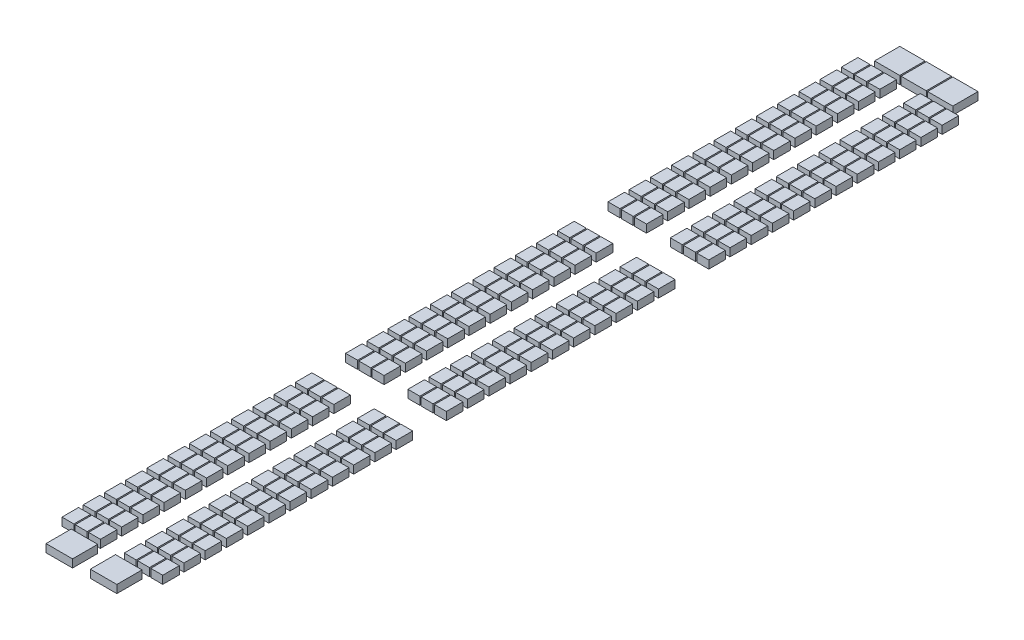
SolidWorks part; units mm, degrees
ref_plane "Front Plane" through (0, 0, 0) normal (0, 0, 1) x (1, 0, 0)
ref_plane "Top Plane" through (0, 0, 0) normal (0, 1, 0) x (1, 0, 0)
ref_plane "Right Plane" through (0, 0, 0) normal (1, 0, 0) x (0, 0, -1)
sketch "Sketch1" plane through (0, 0, 0) normal (0, 1, 0) x (1, 0, 0)
  line L0 (1993.392, 0) -> (-1993.392, 0) construction
  line L1 (1993.392, -15290.8) -> (-1993.392, -15290.8) construction
  line L2 (1993.392, -15290.8) -> (1993.392, 15290.8) construction
  line L3 (1993.392, 15290.8) -> (-1993.392, 15290.8) construction
  line L4 (-1993.392, -15290.8) -> (-1993.392, 15290.8) construction
  line L5 (-1993.392, 5630.3333) -> (1993.392, 5630.3333) construction
  line L6 (-1993.392, 4563.5333) -> (1993.392, 4563.5333) construction
  line L11 (0, -15290.8) -> (0, 15290.8) construction
  line L12 (-1993.392, -4563.5333) -> (1993.392, -4563.5333) construction
  line L13 (-1993.392, -5630.3333) -> (1993.392, -5630.3333) construction
  line L14 (-1421.892, -14613.4667) -> (-964.692, -14613.4667)
  line L15 (-1929.892, -14613.4667) -> (-1472.692, -14613.4667)
  line L16 (-1929.892, -14613.4667) -> (-1929.892, -15248.4667)
  line L17 (-1929.892, -15248.4667) -> (-1472.692, -15248.4667)
  line L18 (-1472.692, -14613.4667) -> (-1472.692, -15248.4667)
  line L19 (-1421.892, -14613.4667) -> (-1421.892, -15248.4667)
  line L20 (-1421.892, -15248.4667) -> (-964.692, -15248.4667)
  line L21 (-964.692, -14613.4667) -> (-964.692, -15248.4667)
  line L22 (-913.892, -14613.4667) -> (-456.692, -14613.4667)
  line L23 (-913.892, -14613.4667) -> (-913.892, -15248.4667)
  line L24 (-913.892, -15248.4667) -> (-456.692, -15248.4667)
  line L25 (-456.692, -14613.4667) -> (-456.692, -15248.4667)
  line L26 (-1421.892, -13800.6667) -> (-964.692, -13800.6667)
  line L27 (-1421.892, -13800.6667) -> (-1421.892, -14435.6667)
  line L28 (-1421.892, -14435.6667) -> (-964.692, -14435.6667)
  line L29 (-964.692, -13800.6667) -> (-964.692, -14435.6667)
  line L30 (-913.892, -13800.6667) -> (-456.692, -13800.6667)
  line L31 (-913.892, -13800.6667) -> (-913.892, -14435.6667)
  line L32 (-913.892, -14435.6667) -> (-456.692, -14435.6667)
  line L33 (-456.692, -13800.6667) -> (-456.692, -14435.6667)
  line L34 (-1421.892, -12987.8667) -> (-964.692, -12987.8667)
  line L35 (-1421.892, -12987.8667) -> (-1421.892, -13622.8667)
  line L36 (-1421.892, -13622.8667) -> (-964.692, -13622.8667)
  line L37 (-964.692, -12987.8667) -> (-964.692, -13622.8667)
  line L38 (-913.892, -12987.8667) -> (-456.692, -12987.8667)
  line L39 (-913.892, -12987.8667) -> (-913.892, -13622.8667)
  line L40 (-913.892, -13622.8667) -> (-456.692, -13622.8667)
  line L41 (-456.692, -12987.8667) -> (-456.692, -13622.8667)
  line L42 (-1929.892, -13800.6667) -> (-1472.692, -13800.6667)
  line L43 (-1929.892, -13800.6667) -> (-1929.892, -14435.6667)
  line L44 (-1929.892, -14435.6667) -> (-1472.692, -14435.6667)
  line L45 (-1472.692, -13800.6667) -> (-1472.692, -14435.6667)
  line L46 (-1929.892, -12987.8667) -> (-1472.692, -12987.8667)
  line L47 (-1929.892, -12987.8667) -> (-1929.892, -13622.8667)
  line L48 (-1929.892, -13622.8667) -> (-1472.692, -13622.8667)
  line L49 (-1472.692, -12987.8667) -> (-1472.692, -13622.8667)
  line L50 (-1929.892, -12175.0667) -> (-1472.692, -12175.0667)
  line L51 (-1929.892, -12175.0667) -> (-1929.892, -12810.0667)
  line L52 (-1929.892, -12810.0667) -> (-1472.692, -12810.0667)
  line L53 (-1472.692, -12175.0667) -> (-1472.692, -12810.0667)
  line L54 (-1421.892, -12175.0667) -> (-964.692, -12175.0667)
  line L55 (-1421.892, -12175.0667) -> (-1421.892, -12810.0667)
  line L56 (-1421.892, -12810.0667) -> (-964.692, -12810.0667)
  line L57 (-964.692, -12175.0667) -> (-964.692, -12810.0667)
  line L58 (-913.892, -12175.0667) -> (-456.692, -12175.0667)
  line L59 (-913.892, -12175.0667) -> (-913.892, -12810.0667)
  line L60 (-913.892, -12810.0667) -> (-456.692, -12810.0667)
  line L61 (-456.692, -12175.0667) -> (-456.692, -12810.0667)
  line L62 (-1929.892, -11362.2667) -> (-1472.692, -11362.2667)
  line L63 (-1929.892, -11362.2667) -> (-1929.892, -11997.2667)
  line L64 (-1929.892, -11997.2667) -> (-1472.692, -11997.2667)
  line L65 (-1472.692, -11362.2667) -> (-1472.692, -11997.2667)
  line L66 (-1421.892, -11362.2667) -> (-964.692, -11362.2667)
  line L67 (-1421.892, -11362.2667) -> (-1421.892, -11997.2667)
  line L68 (-1421.892, -11997.2667) -> (-964.692, -11997.2667)
  line L69 (-964.692, -11362.2667) -> (-964.692, -11997.2667)
  line L70 (-913.892, -11362.2667) -> (-456.692, -11362.2667)
  line L71 (-913.892, -11362.2667) -> (-913.892, -11997.2667)
  line L72 (-913.892, -11997.2667) -> (-456.692, -11997.2667)
  line L73 (-456.692, -11362.2667) -> (-456.692, -11997.2667)
  line L74 (-1929.892, -10549.4667) -> (-1472.692, -10549.4667)
  line L75 (-1929.892, -10549.4667) -> (-1929.892, -11184.4667)
  line L76 (-1929.892, -11184.4667) -> (-1472.692, -11184.4667)
  line L77 (-1472.692, -10549.4667) -> (-1472.692, -11184.4667)
  line L78 (-1421.892, -10549.4667) -> (-964.692, -10549.4667)
  line L79 (-1421.892, -10549.4667) -> (-1421.892, -11184.4667)
  line L80 (-1421.892, -11184.4667) -> (-964.692, -11184.4667)
  line L81 (-964.692, -10549.4667) -> (-964.692, -11184.4667)
  line L82 (-913.892, -10549.4667) -> (-456.692, -10549.4667)
  line L83 (-913.892, -10549.4667) -> (-913.892, -11184.4667)
  line L84 (-913.892, -11184.4667) -> (-456.692, -11184.4667)
  line L85 (-456.692, -10549.4667) -> (-456.692, -11184.4667)
  line L86 (-1929.892, -9736.6667) -> (-1472.692, -9736.6667)
  line L87 (-1929.892, -9736.6667) -> (-1929.892, -10371.6667)
  line L88 (-1929.892, -10371.6667) -> (-1472.692, -10371.6667)
  line L89 (-1472.692, -9736.6667) -> (-1472.692, -10371.6667)
  line L90 (-1421.892, -9736.6667) -> (-964.692, -9736.6667)
  line L91 (-1421.892, -9736.6667) -> (-1421.892, -10371.6667)
  line L92 (-1421.892, -10371.6667) -> (-964.692, -10371.6667)
  line L93 (-964.692, -9736.6667) -> (-964.692, -10371.6667)
  line L94 (-913.892, -9736.6667) -> (-456.692, -9736.6667)
  line L95 (-913.892, -9736.6667) -> (-913.892, -10371.6667)
  line L96 (-913.892, -10371.6667) -> (-456.692, -10371.6667)
  line L97 (-456.692, -9736.6667) -> (-456.692, -10371.6667)
  line L98 (-1929.892, -8923.8667) -> (-1472.692, -8923.8667)
  line L99 (-1929.892, -8923.8667) -> (-1929.892, -9558.8667)
  line L100 (-1929.892, -9558.8667) -> (-1472.692, -9558.8667)
  line L101 (-1472.692, -8923.8667) -> (-1472.692, -9558.8667)
  line L102 (-1421.892, -8923.8667) -> (-964.692, -8923.8667)
  line L103 (-1421.892, -8923.8667) -> (-1421.892, -9558.8667)
  line L104 (-1421.892, -9558.8667) -> (-964.692, -9558.8667)
  line L105 (-964.692, -8923.8667) -> (-964.692, -9558.8667)
  line L106 (-913.892, -8923.8667) -> (-456.692, -8923.8667)
  line L107 (-913.892, -8923.8667) -> (-913.892, -9558.8667)
  line L108 (-913.892, -9558.8667) -> (-456.692, -9558.8667)
  line L109 (-456.692, -8923.8667) -> (-456.692, -9558.8667)
  line L110 (-1929.892, -8111.0667) -> (-1472.692, -8111.0667)
  line L111 (-1929.892, -8111.0667) -> (-1929.892, -8746.0667)
  line L112 (-1929.892, -8746.0667) -> (-1472.692, -8746.0667)
  line L113 (-1472.692, -8111.0667) -> (-1472.692, -8746.0667)
  line L114 (-1421.892, -8111.0667) -> (-964.692, -8111.0667)
  line L115 (-1421.892, -8111.0667) -> (-1421.892, -8746.0667)
  line L116 (-1421.892, -8746.0667) -> (-964.692, -8746.0667)
  line L117 (-964.692, -8111.0667) -> (-964.692, -8746.0667)
  line L118 (-913.892, -8111.0667) -> (-456.692, -8111.0667)
  line L119 (-913.892, -8111.0667) -> (-913.892, -8746.0667)
  line L120 (-913.892, -8746.0667) -> (-456.692, -8746.0667)
  line L121 (-456.692, -8111.0667) -> (-456.692, -8746.0667)
  line L122 (-1929.892, -7298.2667) -> (-1472.692, -7298.2667)
  line L123 (-1929.892, -7298.2667) -> (-1929.892, -7933.2667)
  line L124 (-1929.892, -7933.2667) -> (-1472.692, -7933.2667)
  line L125 (-1472.692, -7298.2667) -> (-1472.692, -7933.2667)
  line L126 (-1421.892, -7298.2667) -> (-964.692, -7298.2667)
  line L127 (-1421.892, -7298.2667) -> (-1421.892, -7933.2667)
  line L128 (-1421.892, -7933.2667) -> (-964.692, -7933.2667)
  line L129 (-964.692, -7298.2667) -> (-964.692, -7933.2667)
  line L130 (-913.892, -7298.2667) -> (-456.692, -7298.2667)
  line L131 (-913.892, -7298.2667) -> (-913.892, -7933.2667)
  line L132 (-913.892, -7933.2667) -> (-456.692, -7933.2667)
  line L133 (-456.692, -7298.2667) -> (-456.692, -7933.2667)
  line L134 (-1929.892, -6485.4667) -> (-1472.692, -6485.4667)
  line L135 (-1929.892, -6485.4667) -> (-1929.892, -7120.4667)
  line L136 (-1929.892, -7120.4667) -> (-1472.692, -7120.4667)
  line L137 (-1472.692, -6485.4667) -> (-1472.692, -7120.4667)
  line L138 (-1421.892, -6485.4667) -> (-964.692, -6485.4667)
  line L139 (-1421.892, -6485.4667) -> (-1421.892, -7120.4667)
  line L140 (-1421.892, -7120.4667) -> (-964.692, -7120.4667)
  line L141 (-964.692, -6485.4667) -> (-964.692, -7120.4667)
  line L142 (-913.892, -6485.4667) -> (-456.692, -6485.4667)
  line L143 (-913.892, -6485.4667) -> (-913.892, -7120.4667)
  line L144 (-913.892, -7120.4667) -> (-456.692, -7120.4667)
  line L145 (-456.692, -6485.4667) -> (-456.692, -7120.4667)
  line L146 (-1929.892, -5672.6667) -> (-1472.692, -5672.6667)
  line L147 (-1929.892, -5672.6667) -> (-1929.892, -6307.6667)
  line L148 (-1929.892, -6307.6667) -> (-1472.692, -6307.6667)
  line L149 (-1472.692, -5672.6667) -> (-1472.692, -6307.6667)
  line L150 (-1421.892, -5672.6667) -> (-964.692, -5672.6667)
  line L151 (-1421.892, -5672.6667) -> (-1421.892, -6307.6667)
  line L152 (-1421.892, -6307.6667) -> (-964.692, -6307.6667)
  line L153 (-964.692, -5672.6667) -> (-964.692, -6307.6667)
  line L154 (-913.892, -5672.6667) -> (-456.692, -5672.6667)
  line L155 (-913.892, -5672.6667) -> (-913.892, -6307.6667)
  line L156 (-913.892, -6307.6667) -> (-456.692, -6307.6667)
  line L157 (-456.692, -5672.6667) -> (-456.692, -6307.6667)
  line L158 (-456.692, -5672.6667) -> (-456.692, -15248.4667) construction
  line L159 (-456.692, -10460.5667) -> (2544.9668, -10460.5667) construction
  line L160 (-1929.892, -3746.5) -> (-1472.692, -3746.5)
  line L161 (-1929.892, -3746.5) -> (-1929.892, -4381.5)
  line L162 (-1929.892, -4381.5) -> (-1472.692, -4381.5)
  line L163 (-1472.692, -3746.5) -> (-1472.692, -4381.5)
  line L164 (-1421.892, -3746.5) -> (-964.692, -3746.5)
  line L165 (-1421.892, -3746.5) -> (-1421.892, -4381.5)
  line L166 (-1421.892, -4381.5) -> (-964.692, -4381.5)
  line L167 (-964.692, -3746.5) -> (-964.692, -4381.5)
  line L168 (-913.892, -3746.5) -> (-456.692, -3746.5)
  line L169 (-913.892, -3746.5) -> (-913.892, -4381.5)
  line L170 (-913.892, -4381.5) -> (-456.692, -4381.5)
  line L171 (-456.692, -3746.5) -> (-456.692, -4381.5)
  line L172 (-1421.892, -2933.7) -> (-964.692, -2933.7)
  line L173 (-1421.892, -2933.7) -> (-1421.892, -3568.7)
  line L174 (-1421.892, -3568.7) -> (-964.692, -3568.7)
  line L175 (-964.692, -2933.7) -> (-964.692, -3568.7)
  line L176 (-913.892, -2933.7) -> (-456.692, -2933.7)
  line L177 (-913.892, -2933.7) -> (-913.892, -3568.7)
  line L178 (-913.892, -3568.7) -> (-456.692, -3568.7)
  line L179 (-456.692, -2933.7) -> (-456.692, -3568.7)
  line L180 (-1421.892, -2120.9) -> (-964.692, -2120.9)
  line L181 (-1421.892, -2120.9) -> (-1421.892, -2755.9)
  line L182 (-1421.892, -2755.9) -> (-964.692, -2755.9)
  line L183 (-964.692, -2120.9) -> (-964.692, -2755.9)
  line L184 (-913.892, -2120.9) -> (-456.692, -2120.9)
  line L185 (-913.892, -2120.9) -> (-913.892, -2755.9)
  line L186 (-913.892, -2755.9) -> (-456.692, -2755.9)
  line L187 (-456.692, -2120.9) -> (-456.692, -2755.9)
  line L188 (-1421.892, -1308.1) -> (-964.692, -1308.1)
  line L189 (-1421.892, -1308.1) -> (-1421.892, -1943.1)
  line L190 (-1421.892, -1943.1) -> (-964.692, -1943.1)
  line L191 (-964.692, -1308.1) -> (-964.692, -1943.1)
  line L192 (-913.892, -1308.1) -> (-456.692, -1308.1)
  line L193 (-913.892, -1308.1) -> (-913.892, -1943.1)
  line L194 (-913.892, -1943.1) -> (-456.692, -1943.1)
  line L195 (-456.692, -1308.1) -> (-456.692, -1943.1)
  line L196 (-1421.892, -495.3) -> (-964.692, -495.3)
  line L197 (-1421.892, -495.3) -> (-1421.892, -1130.3)
  line L198 (-1421.892, -1130.3) -> (-964.692, -1130.3)
  line L199 (-964.692, -495.3) -> (-964.692, -1130.3)
  line L200 (-913.892, -495.3) -> (-456.692, -495.3)
  line L201 (-913.892, -495.3) -> (-913.892, -1130.3)
  line L202 (-913.892, -1130.3) -> (-456.692, -1130.3)
  line L203 (-456.692, -495.3) -> (-456.692, -1130.3)
  line L204 (-1929.892, -2933.7) -> (-1472.692, -2933.7)
  line L205 (-1929.892, -2933.7) -> (-1929.892, -3568.7)
  line L206 (-1929.892, -3568.7) -> (-1472.692, -3568.7)
  line L207 (-1472.692, -2933.7) -> (-1472.692, -3568.7)
  line L208 (-1929.892, -2120.9) -> (-1472.692, -2120.9)
  line L209 (-1929.892, -2120.9) -> (-1929.892, -2755.9)
  line L210 (-1929.892, -2755.9) -> (-1472.692, -2755.9)
  line L211 (-1472.692, -2120.9) -> (-1472.692, -2755.9)
  line L212 (-1929.892, -1308.1) -> (-1472.692, -1308.1)
  line L213 (-1929.892, -1308.1) -> (-1929.892, -1943.1)
  line L214 (-1929.892, -1943.1) -> (-1472.692, -1943.1)
  line L215 (-1472.692, -1308.1) -> (-1472.692, -1943.1)
  line L216 (-1929.892, -495.3) -> (-1472.692, -495.3)
  line L217 (-1929.892, -495.3) -> (-1929.892, -1130.3)
  line L218 (-1929.892, -1130.3) -> (-1472.692, -1130.3)
  line L219 (-1472.692, -495.3) -> (-1472.692, -1130.3)
  line L220 (-1929.892, 317.5) -> (-1472.692, 317.5)
  line L221 (-1929.892, 317.5) -> (-1929.892, -317.5)
  line L222 (-1929.892, -317.5) -> (-1472.692, -317.5)
  line L223 (-1472.692, 317.5) -> (-1472.692, -317.5)
  line L224 (-1421.892, 317.5) -> (-964.692, 317.5)
  line L225 (-1421.892, 317.5) -> (-1421.892, -317.5)
  line L226 (-1421.892, -317.5) -> (-964.692, -317.5)
  line L227 (-964.692, 317.5) -> (-964.692, -317.5)
  line L228 (-913.892, 317.5) -> (-456.692, 317.5)
  line L229 (-913.892, 317.5) -> (-913.892, -317.5)
  line L230 (-913.892, -317.5) -> (-456.692, -317.5)
  line L231 (-456.692, 317.5) -> (-456.692, -317.5)
  line L232 (-1929.892, 1130.3) -> (-1472.692, 1130.3)
  line L233 (-1929.892, 1130.3) -> (-1929.892, 495.3)
  line L234 (-1929.892, 495.3) -> (-1472.692, 495.3)
  line L235 (-1472.692, 1130.3) -> (-1472.692, 495.3)
  line L236 (-1421.892, 1130.3) -> (-964.692, 1130.3)
  line L237 (-1421.892, 1130.3) -> (-1421.892, 495.3)
  line L238 (-1421.892, 495.3) -> (-964.692, 495.3)
  line L239 (-964.692, 1130.3) -> (-964.692, 495.3)
  line L240 (-913.892, 1130.3) -> (-456.692, 1130.3)
  line L241 (-913.892, 1130.3) -> (-913.892, 495.3)
  line L242 (-913.892, 495.3) -> (-456.692, 495.3)
  line L243 (-456.692, 1130.3) -> (-456.692, 495.3)
  line L244 (-1929.892, 1943.1) -> (-1472.692, 1943.1)
  line L245 (-1929.892, 1943.1) -> (-1929.892, 1308.1)
  line L246 (-1929.892, 1308.1) -> (-1472.692, 1308.1)
  line L247 (-1472.692, 1943.1) -> (-1472.692, 1308.1)
  line L248 (-1421.892, 1943.1) -> (-964.692, 1943.1)
  line L249 (-1421.892, 1943.1) -> (-1421.892, 1308.1)
  line L250 (-1421.892, 1308.1) -> (-964.692, 1308.1)
  line L251 (-964.692, 1943.1) -> (-964.692, 1308.1)
  line L252 (-913.892, 1943.1) -> (-456.692, 1943.1)
  line L253 (-913.892, 1943.1) -> (-913.892, 1308.1)
  line L254 (-913.892, 1308.1) -> (-456.692, 1308.1)
  line L255 (-456.692, 1943.1) -> (-456.692, 1308.1)
  line L256 (-1929.892, 2755.9) -> (-1472.692, 2755.9)
  line L257 (-1929.892, 2755.9) -> (-1929.892, 2120.9)
  line L258 (-1929.892, 2120.9) -> (-1472.692, 2120.9)
  line L259 (-1472.692, 2755.9) -> (-1472.692, 2120.9)
  line L260 (-1421.892, 2755.9) -> (-964.692, 2755.9)
  line L261 (-1421.892, 2755.9) -> (-1421.892, 2120.9)
  line L262 (-1421.892, 2120.9) -> (-964.692, 2120.9)
  line L263 (-964.692, 2755.9) -> (-964.692, 2120.9)
  line L264 (-913.892, 2755.9) -> (-456.692, 2755.9)
  line L265 (-913.892, 2755.9) -> (-913.892, 2120.9)
  line L266 (-913.892, 2120.9) -> (-456.692, 2120.9)
  line L267 (-456.692, 2755.9) -> (-456.692, 2120.9)
  line L268 (-1929.892, 3568.7) -> (-1472.692, 3568.7)
  line L269 (-1929.892, 3568.7) -> (-1929.892, 2933.7)
  line L270 (-1929.892, 2933.7) -> (-1472.692, 2933.7)
  line L271 (-1472.692, 3568.7) -> (-1472.692, 2933.7)
  line L272 (-1421.892, 3568.7) -> (-964.692, 3568.7)
  line L273 (-1421.892, 3568.7) -> (-1421.892, 2933.7)
  line L274 (-1421.892, 2933.7) -> (-964.692, 2933.7)
  line L275 (-964.692, 3568.7) -> (-964.692, 2933.7)
  line L276 (-913.892, 3568.7) -> (-456.692, 3568.7)
  line L277 (-913.892, 3568.7) -> (-913.892, 2933.7)
  line L278 (-913.892, 2933.7) -> (-456.692, 2933.7)
  line L279 (-456.692, 3568.7) -> (-456.692, 2933.7)
  line L280 (-1929.892, 4381.5) -> (-1472.692, 4381.5)
  line L281 (-1929.892, 4381.5) -> (-1929.892, 3746.5)
  line L282 (-1929.892, 3746.5) -> (-1472.692, 3746.5)
  line L283 (-1472.692, 4381.5) -> (-1472.692, 3746.5)
  line L284 (-1421.892, 4381.5) -> (-964.692, 4381.5)
  line L285 (-1421.892, 4381.5) -> (-1421.892, 3746.5)
  line L286 (-1421.892, 3746.5) -> (-964.692, 3746.5)
  line L287 (-964.692, 4381.5) -> (-964.692, 3746.5)
  line L288 (-913.892, 4381.5) -> (-456.692, 4381.5)
  line L289 (-913.892, 4381.5) -> (-913.892, 3746.5)
  line L290 (-913.892, 3746.5) -> (-456.692, 3746.5)
  line L291 (-456.692, 4381.5) -> (-456.692, 3746.5)
  line L292 (-456.692, 4381.5) -> (-456.692, -4381.5) construction
  line L293 (-913.892, 15248.4667) -> (-456.692, 15248.4667)
  line L294 (-1421.892, 15248.4667) -> (-964.692, 15248.4667)
  line L295 (-1929.892, 15248.4667) -> (-1472.692, 15248.4667)
  line L296 (-913.892, 5672.6667) -> (-456.692, 5672.6667)
  line L297 (-1421.892, 5672.6667) -> (-964.692, 5672.6667)
  line L298 (-1929.892, 5672.6667) -> (-1472.692, 5672.6667)
  line L299 (-456.692, 10460.5667) -> (2544.9668, 10460.5667) construction
  line L300 (-456.692, 5672.6667) -> (-456.692, 15248.4667) construction
  line L301 (-456.692, 5672.6667) -> (-456.692, 6307.6667)
  line L302 (-913.892, 6307.6667) -> (-456.692, 6307.6667)
  line L303 (-913.892, 5672.6667) -> (-913.892, 6307.6667)
  line L304 (-964.692, 5672.6667) -> (-964.692, 6307.6667)
  line L305 (-1421.892, 6307.6667) -> (-964.692, 6307.6667)
  line L306 (-1421.892, 5672.6667) -> (-1421.892, 6307.6667)
  line L307 (-1472.692, 5672.6667) -> (-1472.692, 6307.6667)
  line L308 (-1929.892, 6307.6667) -> (-1472.692, 6307.6667)
  line L309 (-1929.892, 5672.6667) -> (-1929.892, 6307.6667)
  line L310 (-456.692, 6485.4667) -> (-456.692, 7120.4667)
  line L311 (-913.892, 7120.4667) -> (-456.692, 7120.4667)
  line L312 (-913.892, 6485.4667) -> (-913.892, 7120.4667)
  line L313 (-913.892, 6485.4667) -> (-456.692, 6485.4667)
  line L314 (-964.692, 6485.4667) -> (-964.692, 7120.4667)
  line L315 (-1421.892, 7120.4667) -> (-964.692, 7120.4667)
  line L316 (-1421.892, 6485.4667) -> (-1421.892, 7120.4667)
  line L317 (-1421.892, 6485.4667) -> (-964.692, 6485.4667)
  line L318 (-1472.692, 6485.4667) -> (-1472.692, 7120.4667)
  line L319 (-1929.892, 7120.4667) -> (-1472.692, 7120.4667)
  line L320 (-1929.892, 6485.4667) -> (-1929.892, 7120.4667)
  line L321 (-1929.892, 6485.4667) -> (-1472.692, 6485.4667)
  line L322 (-456.692, 7298.2667) -> (-456.692, 7933.2667)
  line L323 (-913.892, 7933.2667) -> (-456.692, 7933.2667)
  line L324 (-913.892, 7298.2667) -> (-913.892, 7933.2667)
  line L325 (-913.892, 7298.2667) -> (-456.692, 7298.2667)
  line L326 (-964.692, 7298.2667) -> (-964.692, 7933.2667)
  line L327 (-1421.892, 7933.2667) -> (-964.692, 7933.2667)
  line L328 (-1421.892, 7298.2667) -> (-1421.892, 7933.2667)
  line L329 (-1421.892, 7298.2667) -> (-964.692, 7298.2667)
  line L330 (-1472.692, 7298.2667) -> (-1472.692, 7933.2667)
  line L331 (-1929.892, 7933.2667) -> (-1472.692, 7933.2667)
  line L332 (-1929.892, 7298.2667) -> (-1929.892, 7933.2667)
  line L333 (-1929.892, 7298.2667) -> (-1472.692, 7298.2667)
  line L334 (-456.692, 8111.0667) -> (-456.692, 8746.0667)
  line L335 (-913.892, 8746.0667) -> (-456.692, 8746.0667)
  line L336 (-913.892, 8111.0667) -> (-913.892, 8746.0667)
  line L337 (-913.892, 8111.0667) -> (-456.692, 8111.0667)
  line L338 (-964.692, 8111.0667) -> (-964.692, 8746.0667)
  line L339 (-1421.892, 8746.0667) -> (-964.692, 8746.0667)
  line L340 (-1421.892, 8111.0667) -> (-1421.892, 8746.0667)
  line L341 (-1421.892, 8111.0667) -> (-964.692, 8111.0667)
  line L342 (-1472.692, 8111.0667) -> (-1472.692, 8746.0667)
  line L343 (-1929.892, 8746.0667) -> (-1472.692, 8746.0667)
  line L344 (-1929.892, 8111.0667) -> (-1929.892, 8746.0667)
  line L345 (-1929.892, 8111.0667) -> (-1472.692, 8111.0667)
  line L346 (-456.692, 8923.8667) -> (-456.692, 9558.8667)
  line L347 (-913.892, 9558.8667) -> (-456.692, 9558.8667)
  line L348 (-913.892, 8923.8667) -> (-913.892, 9558.8667)
  line L349 (-913.892, 8923.8667) -> (-456.692, 8923.8667)
  line L350 (-964.692, 8923.8667) -> (-964.692, 9558.8667)
  line L351 (-1421.892, 9558.8667) -> (-964.692, 9558.8667)
  line L352 (-1421.892, 8923.8667) -> (-1421.892, 9558.8667)
  line L353 (-1421.892, 8923.8667) -> (-964.692, 8923.8667)
  line L354 (-1472.692, 8923.8667) -> (-1472.692, 9558.8667)
  line L355 (-1929.892, 9558.8667) -> (-1472.692, 9558.8667)
  line L356 (-1929.892, 8923.8667) -> (-1929.892, 9558.8667)
  line L357 (-1929.892, 8923.8667) -> (-1472.692, 8923.8667)
  line L358 (-456.692, 9736.6667) -> (-456.692, 10371.6667)
  line L359 (-913.892, 10371.6667) -> (-456.692, 10371.6667)
  line L360 (-913.892, 9736.6667) -> (-913.892, 10371.6667)
  line L361 (-913.892, 9736.6667) -> (-456.692, 9736.6667)
  line L362 (-964.692, 9736.6667) -> (-964.692, 10371.6667)
  line L363 (-1421.892, 10371.6667) -> (-964.692, 10371.6667)
  line L364 (-1421.892, 9736.6667) -> (-1421.892, 10371.6667)
  line L365 (-1421.892, 9736.6667) -> (-964.692, 9736.6667)
  line L366 (-1472.692, 9736.6667) -> (-1472.692, 10371.6667)
  line L367 (-1929.892, 10371.6667) -> (-1472.692, 10371.6667)
  line L368 (-1929.892, 9736.6667) -> (-1929.892, 10371.6667)
  line L369 (-1929.892, 9736.6667) -> (-1472.692, 9736.6667)
  line L370 (-456.692, 10549.4667) -> (-456.692, 11184.4667)
  line L371 (-913.892, 11184.4667) -> (-456.692, 11184.4667)
  line L372 (-913.892, 10549.4667) -> (-913.892, 11184.4667)
  line L373 (-913.892, 10549.4667) -> (-456.692, 10549.4667)
  line L374 (-964.692, 10549.4667) -> (-964.692, 11184.4667)
  line L375 (-1421.892, 11184.4667) -> (-964.692, 11184.4667)
  line L376 (-1421.892, 10549.4667) -> (-1421.892, 11184.4667)
  line L377 (-1421.892, 10549.4667) -> (-964.692, 10549.4667)
  line L378 (-1472.692, 10549.4667) -> (-1472.692, 11184.4667)
  line L379 (-1929.892, 11184.4667) -> (-1472.692, 11184.4667)
  line L380 (-1929.892, 10549.4667) -> (-1929.892, 11184.4667)
  line L381 (-1929.892, 10549.4667) -> (-1472.692, 10549.4667)
  line L382 (-456.692, 11362.2667) -> (-456.692, 11997.2667)
  line L383 (-913.892, 11997.2667) -> (-456.692, 11997.2667)
  line L384 (-913.892, 11362.2667) -> (-913.892, 11997.2667)
  line L385 (-913.892, 11362.2667) -> (-456.692, 11362.2667)
  line L386 (-964.692, 11362.2667) -> (-964.692, 11997.2667)
  line L387 (-1421.892, 11997.2667) -> (-964.692, 11997.2667)
  line L388 (-1421.892, 11362.2667) -> (-1421.892, 11997.2667)
  line L389 (-1421.892, 11362.2667) -> (-964.692, 11362.2667)
  line L390 (-1472.692, 11362.2667) -> (-1472.692, 11997.2667)
  line L391 (-1929.892, 11997.2667) -> (-1472.692, 11997.2667)
  line L392 (-1929.892, 11362.2667) -> (-1929.892, 11997.2667)
  line L393 (-1929.892, 11362.2667) -> (-1472.692, 11362.2667)
  line L394 (-456.692, 12175.0667) -> (-456.692, 12810.0667)
  line L395 (-913.892, 12810.0667) -> (-456.692, 12810.0667)
  line L396 (-913.892, 12175.0667) -> (-913.892, 12810.0667)
  line L397 (-913.892, 12175.0667) -> (-456.692, 12175.0667)
  line L398 (-964.692, 12175.0667) -> (-964.692, 12810.0667)
  line L399 (-1421.892, 12810.0667) -> (-964.692, 12810.0667)
  line L400 (-1421.892, 12175.0667) -> (-1421.892, 12810.0667)
  line L401 (-1421.892, 12175.0667) -> (-964.692, 12175.0667)
  line L402 (-1472.692, 12175.0667) -> (-1472.692, 12810.0667)
  line L403 (-1929.892, 12810.0667) -> (-1472.692, 12810.0667)
  line L404 (-1929.892, 12175.0667) -> (-1929.892, 12810.0667)
  line L405 (-1929.892, 12175.0667) -> (-1472.692, 12175.0667)
  line L406 (-1472.692, 12987.8667) -> (-1472.692, 13622.8667)
  line L407 (-1929.892, 13622.8667) -> (-1472.692, 13622.8667)
  line L408 (-1929.892, 12987.8667) -> (-1929.892, 13622.8667)
  line L409 (-1929.892, 12987.8667) -> (-1472.692, 12987.8667)
  line L410 (-1472.692, 13800.6667) -> (-1472.692, 14435.6667)
  line L411 (-1929.892, 14435.6667) -> (-1472.692, 14435.6667)
  line L412 (-1929.892, 13800.6667) -> (-1929.892, 14435.6667)
  line L413 (-1929.892, 13800.6667) -> (-1472.692, 13800.6667)
  line L414 (-456.692, 12987.8667) -> (-456.692, 13622.8667)
  line L415 (-913.892, 13622.8667) -> (-456.692, 13622.8667)
  line L416 (-913.892, 12987.8667) -> (-913.892, 13622.8667)
  line L417 (-913.892, 12987.8667) -> (-456.692, 12987.8667)
  line L418 (-964.692, 12987.8667) -> (-964.692, 13622.8667)
  line L419 (-1421.892, 13622.8667) -> (-964.692, 13622.8667)
  line L420 (-1421.892, 12987.8667) -> (-1421.892, 13622.8667)
  line L421 (-1421.892, 12987.8667) -> (-964.692, 12987.8667)
  line L422 (-456.692, 13800.6667) -> (-456.692, 14435.6667)
  line L423 (-913.892, 14435.6667) -> (-456.692, 14435.6667)
  line L424 (-913.892, 13800.6667) -> (-913.892, 14435.6667)
  line L425 (-913.892, 13800.6667) -> (-456.692, 13800.6667)
  line L426 (-964.692, 13800.6667) -> (-964.692, 14435.6667)
  line L427 (-1421.892, 14435.6667) -> (-964.692, 14435.6667)
  line L428 (-1421.892, 13800.6667) -> (-1421.892, 14435.6667)
  line L429 (-1421.892, 13800.6667) -> (-964.692, 13800.6667)
  line L430 (-456.692, 14613.4667) -> (-456.692, 15248.4667)
  line L431 (-913.892, 14613.4667) -> (-913.892, 15248.4667)
  line L432 (-913.892, 14613.4667) -> (-456.692, 14613.4667)
  line L433 (-964.692, 14613.4667) -> (-964.692, 15248.4667)
  line L434 (-1421.892, 14613.4667) -> (-1421.892, 15248.4667)
  line L435 (-1472.692, 14613.4667) -> (-1472.692, 15248.4667)
  line L436 (-1929.892, 14613.4667) -> (-1929.892, 15248.4667)
  line L437 (-1929.892, 14613.4667) -> (-1472.692, 14613.4667)
  line L438 (-1421.892, 14613.4667) -> (-964.692, 14613.4667)
  line L439 (456.692, 5672.6667) -> (456.692, 15248.4667) construction
  line L440 (456.692, 4381.5) -> (456.692, -4381.5) construction
  line L441 (456.692, -5672.6667) -> (456.692, -15248.4667) construction
  line L442 (1421.892, 14613.4667) -> (964.692, 14613.4667)
  line L443 (1929.892, 14613.4667) -> (1472.692, 14613.4667)
  line L444 (1929.892, 14613.4667) -> (1929.892, 15248.4667)
  line L445 (1472.692, 14613.4667) -> (1472.692, 15248.4667)
  line L446 (1421.892, 14613.4667) -> (1421.892, 15248.4667)
  line L447 (964.692, 14613.4667) -> (964.692, 15248.4667)
  line L448 (913.892, 14613.4667) -> (456.692, 14613.4667)
  line L449 (913.892, 14613.4667) -> (913.892, 15248.4667)
  line L450 (456.692, 14613.4667) -> (456.692, 15248.4667)
  line L451 (1421.892, 13800.6667) -> (964.692, 13800.6667)
  line L452 (1421.892, 13800.6667) -> (1421.892, 14435.6667)
  line L453 (1421.892, 14435.6667) -> (964.692, 14435.6667)
  line L454 (964.692, 13800.6667) -> (964.692, 14435.6667)
  line L455 (913.892, 13800.6667) -> (456.692, 13800.6667)
  line L456 (913.892, 13800.6667) -> (913.892, 14435.6667)
  line L457 (913.892, 14435.6667) -> (456.692, 14435.6667)
  line L458 (456.692, 13800.6667) -> (456.692, 14435.6667)
  line L459 (1421.892, 12987.8667) -> (964.692, 12987.8667)
  line L460 (1421.892, 12987.8667) -> (1421.892, 13622.8667)
  line L461 (1421.892, 13622.8667) -> (964.692, 13622.8667)
  line L462 (964.692, 12987.8667) -> (964.692, 13622.8667)
  line L463 (913.892, 12987.8667) -> (456.692, 12987.8667)
  line L464 (913.892, 12987.8667) -> (913.892, 13622.8667)
  line L465 (913.892, 13622.8667) -> (456.692, 13622.8667)
  line L466 (456.692, 12987.8667) -> (456.692, 13622.8667)
  line L467 (1929.892, 13800.6667) -> (1472.692, 13800.6667)
  line L468 (1929.892, 13800.6667) -> (1929.892, 14435.6667)
  line L469 (1929.892, 14435.6667) -> (1472.692, 14435.6667)
  line L470 (1472.692, 13800.6667) -> (1472.692, 14435.6667)
  line L471 (1929.892, 12987.8667) -> (1472.692, 12987.8667)
  line L472 (1929.892, 12987.8667) -> (1929.892, 13622.8667)
  line L473 (1929.892, 13622.8667) -> (1472.692, 13622.8667)
  line L474 (1472.692, 12987.8667) -> (1472.692, 13622.8667)
  line L475 (1929.892, 12175.0667) -> (1472.692, 12175.0667)
  line L476 (1929.892, 12175.0667) -> (1929.892, 12810.0667)
  line L477 (1929.892, 12810.0667) -> (1472.692, 12810.0667)
  line L478 (1472.692, 12175.0667) -> (1472.692, 12810.0667)
  line L479 (1421.892, 12175.0667) -> (964.692, 12175.0667)
  line L480 (1421.892, 12175.0667) -> (1421.892, 12810.0667)
  line L481 (1421.892, 12810.0667) -> (964.692, 12810.0667)
  line L482 (964.692, 12175.0667) -> (964.692, 12810.0667)
  line L483 (913.892, 12175.0667) -> (456.692, 12175.0667)
  line L484 (913.892, 12175.0667) -> (913.892, 12810.0667)
  line L485 (913.892, 12810.0667) -> (456.692, 12810.0667)
  line L486 (456.692, 12175.0667) -> (456.692, 12810.0667)
  line L487 (1929.892, 11362.2667) -> (1472.692, 11362.2667)
  line L488 (1929.892, 11362.2667) -> (1929.892, 11997.2667)
  line L489 (1929.892, 11997.2667) -> (1472.692, 11997.2667)
  line L490 (1472.692, 11362.2667) -> (1472.692, 11997.2667)
  line L491 (1421.892, 11362.2667) -> (964.692, 11362.2667)
  line L492 (1421.892, 11362.2667) -> (1421.892, 11997.2667)
  line L493 (1421.892, 11997.2667) -> (964.692, 11997.2667)
  line L494 (964.692, 11362.2667) -> (964.692, 11997.2667)
  line L495 (913.892, 11362.2667) -> (456.692, 11362.2667)
  line L496 (913.892, 11362.2667) -> (913.892, 11997.2667)
  line L497 (913.892, 11997.2667) -> (456.692, 11997.2667)
  line L498 (456.692, 11362.2667) -> (456.692, 11997.2667)
  line L499 (1929.892, 10549.4667) -> (1472.692, 10549.4667)
  line L500 (1929.892, 10549.4667) -> (1929.892, 11184.4667)
  line L501 (1929.892, 11184.4667) -> (1472.692, 11184.4667)
  line L502 (1472.692, 10549.4667) -> (1472.692, 11184.4667)
  line L503 (1421.892, 10549.4667) -> (964.692, 10549.4667)
  line L504 (1421.892, 10549.4667) -> (1421.892, 11184.4667)
  line L505 (1421.892, 11184.4667) -> (964.692, 11184.4667)
  line L506 (964.692, 10549.4667) -> (964.692, 11184.4667)
  line L507 (913.892, 10549.4667) -> (456.692, 10549.4667)
  line L508 (913.892, 10549.4667) -> (913.892, 11184.4667)
  line L509 (913.892, 11184.4667) -> (456.692, 11184.4667)
  line L510 (456.692, 10549.4667) -> (456.692, 11184.4667)
  line L511 (1929.892, 9736.6667) -> (1472.692, 9736.6667)
  line L512 (1929.892, 9736.6667) -> (1929.892, 10371.6667)
  line L513 (1929.892, 10371.6667) -> (1472.692, 10371.6667)
  line L514 (1472.692, 9736.6667) -> (1472.692, 10371.6667)
  line L515 (1421.892, 9736.6667) -> (964.692, 9736.6667)
  line L516 (1421.892, 9736.6667) -> (1421.892, 10371.6667)
  line L517 (1421.892, 10371.6667) -> (964.692, 10371.6667)
  line L518 (964.692, 9736.6667) -> (964.692, 10371.6667)
  line L519 (913.892, 9736.6667) -> (456.692, 9736.6667)
  line L520 (913.892, 9736.6667) -> (913.892, 10371.6667)
  line L521 (913.892, 10371.6667) -> (456.692, 10371.6667)
  line L522 (456.692, 9736.6667) -> (456.692, 10371.6667)
  line L523 (1929.892, 8923.8667) -> (1472.692, 8923.8667)
  line L524 (1929.892, 8923.8667) -> (1929.892, 9558.8667)
  line L525 (1929.892, 9558.8667) -> (1472.692, 9558.8667)
  line L526 (1472.692, 8923.8667) -> (1472.692, 9558.8667)
  line L527 (1421.892, 8923.8667) -> (964.692, 8923.8667)
  line L528 (1421.892, 8923.8667) -> (1421.892, 9558.8667)
  line L529 (1421.892, 9558.8667) -> (964.692, 9558.8667)
  line L530 (964.692, 8923.8667) -> (964.692, 9558.8667)
  line L531 (913.892, 8923.8667) -> (456.692, 8923.8667)
  line L532 (913.892, 8923.8667) -> (913.892, 9558.8667)
  line L533 (913.892, 9558.8667) -> (456.692, 9558.8667)
  line L534 (456.692, 8923.8667) -> (456.692, 9558.8667)
  line L535 (1929.892, 8111.0667) -> (1472.692, 8111.0667)
  line L536 (1929.892, 8111.0667) -> (1929.892, 8746.0667)
  line L537 (1929.892, 8746.0667) -> (1472.692, 8746.0667)
  line L538 (1472.692, 8111.0667) -> (1472.692, 8746.0667)
  line L539 (1421.892, 8111.0667) -> (964.692, 8111.0667)
  line L540 (1421.892, 8111.0667) -> (1421.892, 8746.0667)
  line L541 (1421.892, 8746.0667) -> (964.692, 8746.0667)
  line L542 (964.692, 8111.0667) -> (964.692, 8746.0667)
  line L543 (913.892, 8111.0667) -> (456.692, 8111.0667)
  line L544 (913.892, 8111.0667) -> (913.892, 8746.0667)
  line L545 (913.892, 8746.0667) -> (456.692, 8746.0667)
  line L546 (456.692, 8111.0667) -> (456.692, 8746.0667)
  line L547 (1929.892, 7298.2667) -> (1472.692, 7298.2667)
  line L548 (1929.892, 7298.2667) -> (1929.892, 7933.2667)
  line L549 (1929.892, 7933.2667) -> (1472.692, 7933.2667)
  line L550 (1472.692, 7298.2667) -> (1472.692, 7933.2667)
  line L551 (1421.892, 7298.2667) -> (964.692, 7298.2667)
  line L552 (1421.892, 7298.2667) -> (1421.892, 7933.2667)
  line L553 (1421.892, 7933.2667) -> (964.692, 7933.2667)
  line L554 (964.692, 7298.2667) -> (964.692, 7933.2667)
  line L555 (913.892, 7298.2667) -> (456.692, 7298.2667)
  line L556 (913.892, 7298.2667) -> (913.892, 7933.2667)
  line L557 (913.892, 7933.2667) -> (456.692, 7933.2667)
  line L558 (456.692, 7298.2667) -> (456.692, 7933.2667)
  line L559 (1929.892, 6485.4667) -> (1472.692, 6485.4667)
  line L560 (1929.892, 6485.4667) -> (1929.892, 7120.4667)
  line L561 (1929.892, 7120.4667) -> (1472.692, 7120.4667)
  line L562 (1472.692, 6485.4667) -> (1472.692, 7120.4667)
  line L563 (1421.892, 6485.4667) -> (964.692, 6485.4667)
  line L564 (1421.892, 6485.4667) -> (1421.892, 7120.4667)
  line L565 (1421.892, 7120.4667) -> (964.692, 7120.4667)
  line L566 (964.692, 6485.4667) -> (964.692, 7120.4667)
  line L567 (913.892, 6485.4667) -> (456.692, 6485.4667)
  line L568 (913.892, 6485.4667) -> (913.892, 7120.4667)
  line L569 (913.892, 7120.4667) -> (456.692, 7120.4667)
  line L570 (456.692, 6485.4667) -> (456.692, 7120.4667)
  line L571 (1929.892, 5672.6667) -> (1929.892, 6307.6667)
  line L572 (1929.892, 6307.6667) -> (1472.692, 6307.6667)
  line L573 (1472.692, 5672.6667) -> (1472.692, 6307.6667)
  line L574 (1421.892, 5672.6667) -> (1421.892, 6307.6667)
  line L575 (1421.892, 6307.6667) -> (964.692, 6307.6667)
  line L576 (964.692, 5672.6667) -> (964.692, 6307.6667)
  line L577 (913.892, 5672.6667) -> (913.892, 6307.6667)
  line L578 (913.892, 6307.6667) -> (456.692, 6307.6667)
  line L579 (456.692, 5672.6667) -> (456.692, 6307.6667)
  line L580 (1929.892, 5672.6667) -> (1472.692, 5672.6667)
  line L581 (1421.892, 5672.6667) -> (964.692, 5672.6667)
  line L582 (913.892, 5672.6667) -> (456.692, 5672.6667)
  line L583 (1929.892, 15248.4667) -> (1472.692, 15248.4667)
  line L584 (1421.892, 15248.4667) -> (964.692, 15248.4667)
  line L585 (913.892, 15248.4667) -> (456.692, 15248.4667)
  line L586 (456.692, 4381.5) -> (456.692, 3746.5)
  line L587 (913.892, 3746.5) -> (456.692, 3746.5)
  line L588 (913.892, 4381.5) -> (913.892, 3746.5)
  line L589 (913.892, 4381.5) -> (456.692, 4381.5)
  line L590 (964.692, 4381.5) -> (964.692, 3746.5)
  line L591 (1421.892, 3746.5) -> (964.692, 3746.5)
  line L592 (1421.892, 4381.5) -> (1421.892, 3746.5)
  line L593 (1421.892, 4381.5) -> (964.692, 4381.5)
  line L594 (1472.692, 4381.5) -> (1472.692, 3746.5)
  line L595 (1929.892, 3746.5) -> (1472.692, 3746.5)
  line L596 (1929.892, 4381.5) -> (1929.892, 3746.5)
  line L597 (1929.892, 4381.5) -> (1472.692, 4381.5)
  line L598 (456.692, 3568.7) -> (456.692, 2933.7)
  line L599 (913.892, 2933.7) -> (456.692, 2933.7)
  line L600 (913.892, 3568.7) -> (913.892, 2933.7)
  line L601 (913.892, 3568.7) -> (456.692, 3568.7)
  line L602 (964.692, 3568.7) -> (964.692, 2933.7)
  line L603 (1421.892, 2933.7) -> (964.692, 2933.7)
  line L604 (1421.892, 3568.7) -> (1421.892, 2933.7)
  line L605 (1421.892, 3568.7) -> (964.692, 3568.7)
  line L606 (1472.692, 3568.7) -> (1472.692, 2933.7)
  line L607 (1929.892, 2933.7) -> (1472.692, 2933.7)
  line L608 (1929.892, 3568.7) -> (1929.892, 2933.7)
  line L609 (1929.892, 3568.7) -> (1472.692, 3568.7)
  line L610 (456.692, 2755.9) -> (456.692, 2120.9)
  line L611 (913.892, 2120.9) -> (456.692, 2120.9)
  line L612 (913.892, 2755.9) -> (913.892, 2120.9)
  line L613 (913.892, 2755.9) -> (456.692, 2755.9)
  line L614 (964.692, 2755.9) -> (964.692, 2120.9)
  line L615 (1421.892, 2120.9) -> (964.692, 2120.9)
  line L616 (1421.892, 2755.9) -> (1421.892, 2120.9)
  line L617 (1421.892, 2755.9) -> (964.692, 2755.9)
  line L618 (1472.692, 2755.9) -> (1472.692, 2120.9)
  line L619 (1929.892, 2120.9) -> (1472.692, 2120.9)
  line L620 (1929.892, 2755.9) -> (1929.892, 2120.9)
  line L621 (1929.892, 2755.9) -> (1472.692, 2755.9)
  line L622 (456.692, 1943.1) -> (456.692, 1308.1)
  line L623 (913.892, 1308.1) -> (456.692, 1308.1)
  line L624 (913.892, 1943.1) -> (913.892, 1308.1)
  line L625 (913.892, 1943.1) -> (456.692, 1943.1)
  line L626 (964.692, 1943.1) -> (964.692, 1308.1)
  line L627 (1421.892, 1308.1) -> (964.692, 1308.1)
  line L628 (1421.892, 1943.1) -> (1421.892, 1308.1)
  line L629 (1421.892, 1943.1) -> (964.692, 1943.1)
  line L630 (1472.692, 1943.1) -> (1472.692, 1308.1)
  line L631 (1929.892, 1308.1) -> (1472.692, 1308.1)
  line L632 (1929.892, 1943.1) -> (1929.892, 1308.1)
  line L633 (1929.892, 1943.1) -> (1472.692, 1943.1)
  line L634 (456.692, 1130.3) -> (456.692, 495.3)
  line L635 (913.892, 495.3) -> (456.692, 495.3)
  line L636 (913.892, 1130.3) -> (913.892, 495.3)
  line L637 (913.892, 1130.3) -> (456.692, 1130.3)
  line L638 (964.692, 1130.3) -> (964.692, 495.3)
  line L639 (1421.892, 495.3) -> (964.692, 495.3)
  line L640 (1421.892, 1130.3) -> (1421.892, 495.3)
  line L641 (1421.892, 1130.3) -> (964.692, 1130.3)
  line L642 (1472.692, 1130.3) -> (1472.692, 495.3)
  line L643 (1929.892, 495.3) -> (1472.692, 495.3)
  line L644 (1929.892, 1130.3) -> (1929.892, 495.3)
  line L645 (1929.892, 1130.3) -> (1472.692, 1130.3)
  line L646 (456.692, 317.5) -> (456.692, -317.5)
  line L647 (913.892, -317.5) -> (456.692, -317.5)
  line L648 (913.892, 317.5) -> (913.892, -317.5)
  line L649 (913.892, 317.5) -> (456.692, 317.5)
  line L650 (964.692, 317.5) -> (964.692, -317.5)
  line L651 (1421.892, -317.5) -> (964.692, -317.5)
  line L652 (1421.892, 317.5) -> (1421.892, -317.5)
  line L653 (1421.892, 317.5) -> (964.692, 317.5)
  line L654 (1472.692, 317.5) -> (1472.692, -317.5)
  line L655 (1929.892, -317.5) -> (1472.692, -317.5)
  line L656 (1929.892, 317.5) -> (1929.892, -317.5)
  line L657 (1929.892, 317.5) -> (1472.692, 317.5)
  line L658 (1472.692, -495.3) -> (1472.692, -1130.3)
  line L659 (1929.892, -1130.3) -> (1472.692, -1130.3)
  line L660 (1929.892, -495.3) -> (1929.892, -1130.3)
  line L661 (1929.892, -495.3) -> (1472.692, -495.3)
  line L662 (1472.692, -1308.1) -> (1472.692, -1943.1)
  line L663 (1929.892, -1943.1) -> (1472.692, -1943.1)
  line L664 (1929.892, -1308.1) -> (1929.892, -1943.1)
  line L665 (1929.892, -1308.1) -> (1472.692, -1308.1)
  line L666 (1472.692, -2120.9) -> (1472.692, -2755.9)
  line L667 (1929.892, -2755.9) -> (1472.692, -2755.9)
  line L668 (1929.892, -2120.9) -> (1929.892, -2755.9)
  line L669 (1929.892, -2120.9) -> (1472.692, -2120.9)
  line L670 (1472.692, -2933.7) -> (1472.692, -3568.7)
  line L671 (1929.892, -3568.7) -> (1472.692, -3568.7)
  line L672 (1929.892, -2933.7) -> (1929.892, -3568.7)
  line L673 (1929.892, -2933.7) -> (1472.692, -2933.7)
  line L674 (456.692, -495.3) -> (456.692, -1130.3)
  line L675 (913.892, -1130.3) -> (456.692, -1130.3)
  line L676 (913.892, -495.3) -> (913.892, -1130.3)
  line L677 (913.892, -495.3) -> (456.692, -495.3)
  line L678 (964.692, -495.3) -> (964.692, -1130.3)
  line L679 (1421.892, -1130.3) -> (964.692, -1130.3)
  line L680 (1421.892, -495.3) -> (1421.892, -1130.3)
  line L681 (1421.892, -495.3) -> (964.692, -495.3)
  line L682 (456.692, -1308.1) -> (456.692, -1943.1)
  line L683 (913.892, -1943.1) -> (456.692, -1943.1)
  line L684 (913.892, -1308.1) -> (913.892, -1943.1)
  line L685 (913.892, -1308.1) -> (456.692, -1308.1)
  line L686 (964.692, -1308.1) -> (964.692, -1943.1)
  line L687 (1421.892, -1943.1) -> (964.692, -1943.1)
  line L688 (1421.892, -1308.1) -> (1421.892, -1943.1)
  line L689 (1421.892, -1308.1) -> (964.692, -1308.1)
  line L690 (456.692, -2120.9) -> (456.692, -2755.9)
  line L691 (913.892, -2755.9) -> (456.692, -2755.9)
  line L692 (913.892, -2120.9) -> (913.892, -2755.9)
  line L693 (913.892, -2120.9) -> (456.692, -2120.9)
  line L694 (964.692, -2120.9) -> (964.692, -2755.9)
  line L695 (1421.892, -2755.9) -> (964.692, -2755.9)
  line L696 (1421.892, -2120.9) -> (1421.892, -2755.9)
  line L697 (1421.892, -2120.9) -> (964.692, -2120.9)
  line L698 (456.692, -2933.7) -> (456.692, -3568.7)
  line L699 (913.892, -3568.7) -> (456.692, -3568.7)
  line L700 (913.892, -2933.7) -> (913.892, -3568.7)
  line L701 (913.892, -2933.7) -> (456.692, -2933.7)
  line L702 (964.692, -2933.7) -> (964.692, -3568.7)
  line L703 (1421.892, -3568.7) -> (964.692, -3568.7)
  line L704 (1421.892, -2933.7) -> (1421.892, -3568.7)
  line L705 (1421.892, -2933.7) -> (964.692, -2933.7)
  line L706 (456.692, -3746.5) -> (456.692, -4381.5)
  line L707 (913.892, -4381.5) -> (456.692, -4381.5)
  line L708 (913.892, -3746.5) -> (913.892, -4381.5)
  line L709 (913.892, -3746.5) -> (456.692, -3746.5)
  line L710 (964.692, -3746.5) -> (964.692, -4381.5)
  line L711 (1421.892, -4381.5) -> (964.692, -4381.5)
  line L712 (1421.892, -3746.5) -> (1421.892, -4381.5)
  line L713 (1421.892, -3746.5) -> (964.692, -3746.5)
  line L714 (1472.692, -3746.5) -> (1472.692, -4381.5)
  line L715 (1929.892, -4381.5) -> (1472.692, -4381.5)
  line L716 (1929.892, -3746.5) -> (1929.892, -4381.5)
  line L717 (1929.892, -3746.5) -> (1472.692, -3746.5)
  line L718 (456.692, -5672.6667) -> (456.692, -6307.6667)
  line L719 (913.892, -6307.6667) -> (456.692, -6307.6667)
  line L720 (913.892, -5672.6667) -> (913.892, -6307.6667)
  line L721 (913.892, -5672.6667) -> (456.692, -5672.6667)
  line L722 (964.692, -5672.6667) -> (964.692, -6307.6667)
  line L723 (1421.892, -6307.6667) -> (964.692, -6307.6667)
  line L724 (1421.892, -5672.6667) -> (1421.892, -6307.6667)
  line L725 (1421.892, -5672.6667) -> (964.692, -5672.6667)
  line L726 (1472.692, -5672.6667) -> (1472.692, -6307.6667)
  line L727 (1929.892, -6307.6667) -> (1472.692, -6307.6667)
  line L728 (1929.892, -5672.6667) -> (1929.892, -6307.6667)
  line L729 (1929.892, -5672.6667) -> (1472.692, -5672.6667)
  line L730 (456.692, -6485.4667) -> (456.692, -7120.4667)
  line L731 (913.892, -7120.4667) -> (456.692, -7120.4667)
  line L732 (913.892, -6485.4667) -> (913.892, -7120.4667)
  line L733 (913.892, -6485.4667) -> (456.692, -6485.4667)
  line L734 (964.692, -6485.4667) -> (964.692, -7120.4667)
  line L735 (1421.892, -7120.4667) -> (964.692, -7120.4667)
  line L736 (1421.892, -6485.4667) -> (1421.892, -7120.4667)
  line L737 (1421.892, -6485.4667) -> (964.692, -6485.4667)
  line L738 (1472.692, -6485.4667) -> (1472.692, -7120.4667)
  line L739 (1929.892, -7120.4667) -> (1472.692, -7120.4667)
  line L740 (1929.892, -6485.4667) -> (1929.892, -7120.4667)
  line L741 (1929.892, -6485.4667) -> (1472.692, -6485.4667)
  line L742 (456.692, -7298.2667) -> (456.692, -7933.2667)
  line L743 (913.892, -7933.2667) -> (456.692, -7933.2667)
  line L744 (913.892, -7298.2667) -> (913.892, -7933.2667)
  line L745 (913.892, -7298.2667) -> (456.692, -7298.2667)
  line L746 (964.692, -7298.2667) -> (964.692, -7933.2667)
  line L747 (1421.892, -7933.2667) -> (964.692, -7933.2667)
  line L748 (1421.892, -7298.2667) -> (1421.892, -7933.2667)
  line L749 (1421.892, -7298.2667) -> (964.692, -7298.2667)
  line L750 (1472.692, -7298.2667) -> (1472.692, -7933.2667)
  line L751 (1929.892, -7933.2667) -> (1472.692, -7933.2667)
  line L752 (1929.892, -7298.2667) -> (1929.892, -7933.2667)
  line L753 (1929.892, -7298.2667) -> (1472.692, -7298.2667)
  line L754 (456.692, -8111.0667) -> (456.692, -8746.0667)
  line L755 (913.892, -8746.0667) -> (456.692, -8746.0667)
  line L756 (913.892, -8111.0667) -> (913.892, -8746.0667)
  line L757 (913.892, -8111.0667) -> (456.692, -8111.0667)
  line L758 (964.692, -8111.0667) -> (964.692, -8746.0667)
  line L759 (1421.892, -8746.0667) -> (964.692, -8746.0667)
  line L760 (1421.892, -8111.0667) -> (1421.892, -8746.0667)
  line L761 (1421.892, -8111.0667) -> (964.692, -8111.0667)
  line L762 (1472.692, -8111.0667) -> (1472.692, -8746.0667)
  line L763 (1929.892, -8746.0667) -> (1472.692, -8746.0667)
  line L764 (1929.892, -8111.0667) -> (1929.892, -8746.0667)
  line L765 (1929.892, -8111.0667) -> (1472.692, -8111.0667)
  line L766 (456.692, -8923.8667) -> (456.692, -9558.8667)
  line L767 (913.892, -9558.8667) -> (456.692, -9558.8667)
  line L768 (913.892, -8923.8667) -> (913.892, -9558.8667)
  line L769 (913.892, -8923.8667) -> (456.692, -8923.8667)
  line L770 (964.692, -8923.8667) -> (964.692, -9558.8667)
  line L771 (1421.892, -9558.8667) -> (964.692, -9558.8667)
  line L772 (1421.892, -8923.8667) -> (1421.892, -9558.8667)
  line L773 (1421.892, -8923.8667) -> (964.692, -8923.8667)
  line L774 (1472.692, -8923.8667) -> (1472.692, -9558.8667)
  line L775 (1929.892, -9558.8667) -> (1472.692, -9558.8667)
  line L776 (1929.892, -8923.8667) -> (1929.892, -9558.8667)
  line L777 (1929.892, -8923.8667) -> (1472.692, -8923.8667)
  line L778 (456.692, -9736.6667) -> (456.692, -10371.6667)
  line L779 (913.892, -10371.6667) -> (456.692, -10371.6667)
  line L780 (913.892, -9736.6667) -> (913.892, -10371.6667)
  line L781 (913.892, -9736.6667) -> (456.692, -9736.6667)
  line L782 (964.692, -9736.6667) -> (964.692, -10371.6667)
  line L783 (1421.892, -10371.6667) -> (964.692, -10371.6667)
  line L784 (1421.892, -9736.6667) -> (1421.892, -10371.6667)
  line L785 (1421.892, -9736.6667) -> (964.692, -9736.6667)
  line L786 (1472.692, -9736.6667) -> (1472.692, -10371.6667)
  line L787 (1929.892, -10371.6667) -> (1472.692, -10371.6667)
  line L788 (1929.892, -9736.6667) -> (1929.892, -10371.6667)
  line L789 (1929.892, -9736.6667) -> (1472.692, -9736.6667)
  line L790 (456.692, -10549.4667) -> (456.692, -11184.4667)
  line L791 (913.892, -11184.4667) -> (456.692, -11184.4667)
  line L792 (913.892, -10549.4667) -> (913.892, -11184.4667)
  line L793 (913.892, -10549.4667) -> (456.692, -10549.4667)
  line L794 (964.692, -10549.4667) -> (964.692, -11184.4667)
  line L795 (1421.892, -11184.4667) -> (964.692, -11184.4667)
  line L796 (1421.892, -10549.4667) -> (1421.892, -11184.4667)
  line L797 (1421.892, -10549.4667) -> (964.692, -10549.4667)
  line L798 (1472.692, -10549.4667) -> (1472.692, -11184.4667)
  line L799 (1929.892, -11184.4667) -> (1472.692, -11184.4667)
  line L800 (1929.892, -10549.4667) -> (1929.892, -11184.4667)
  line L801 (1929.892, -10549.4667) -> (1472.692, -10549.4667)
  line L802 (456.692, -11362.2667) -> (456.692, -11997.2667)
  line L803 (913.892, -11997.2667) -> (456.692, -11997.2667)
  line L804 (913.892, -11362.2667) -> (913.892, -11997.2667)
  line L805 (913.892, -11362.2667) -> (456.692, -11362.2667)
  line L806 (964.692, -11362.2667) -> (964.692, -11997.2667)
  line L807 (1421.892, -11997.2667) -> (964.692, -11997.2667)
  line L808 (1421.892, -11362.2667) -> (1421.892, -11997.2667)
  line L809 (1421.892, -11362.2667) -> (964.692, -11362.2667)
  line L810 (1472.692, -11362.2667) -> (1472.692, -11997.2667)
  line L811 (1929.892, -11997.2667) -> (1472.692, -11997.2667)
  line L812 (1929.892, -11362.2667) -> (1929.892, -11997.2667)
  line L813 (1929.892, -11362.2667) -> (1472.692, -11362.2667)
  line L814 (456.692, -12175.0667) -> (456.692, -12810.0667)
  line L815 (913.892, -12810.0667) -> (456.692, -12810.0667)
  line L816 (913.892, -12175.0667) -> (913.892, -12810.0667)
  line L817 (913.892, -12175.0667) -> (456.692, -12175.0667)
  line L818 (964.692, -12175.0667) -> (964.692, -12810.0667)
  line L819 (1421.892, -12810.0667) -> (964.692, -12810.0667)
  line L820 (1421.892, -12175.0667) -> (1421.892, -12810.0667)
  line L821 (1421.892, -12175.0667) -> (964.692, -12175.0667)
  line L822 (1472.692, -12175.0667) -> (1472.692, -12810.0667)
  line L823 (1929.892, -12810.0667) -> (1472.692, -12810.0667)
  line L824 (1929.892, -12175.0667) -> (1929.892, -12810.0667)
  line L825 (1929.892, -12175.0667) -> (1472.692, -12175.0667)
  line L826 (1472.692, -12987.8667) -> (1472.692, -13622.8667)
  line L827 (1929.892, -13622.8667) -> (1472.692, -13622.8667)
  line L828 (1929.892, -12987.8667) -> (1929.892, -13622.8667)
  line L829 (1929.892, -12987.8667) -> (1472.692, -12987.8667)
  line L830 (1472.692, -13800.6667) -> (1472.692, -14435.6667)
  line L831 (1929.892, -14435.6667) -> (1472.692, -14435.6667)
  line L832 (1929.892, -13800.6667) -> (1929.892, -14435.6667)
  line L833 (1929.892, -13800.6667) -> (1472.692, -13800.6667)
  line L834 (456.692, -12987.8667) -> (456.692, -13622.8667)
  line L835 (913.892, -13622.8667) -> (456.692, -13622.8667)
  line L836 (913.892, -12987.8667) -> (913.892, -13622.8667)
  line L837 (913.892, -12987.8667) -> (456.692, -12987.8667)
  line L838 (964.692, -12987.8667) -> (964.692, -13622.8667)
  line L839 (1421.892, -13622.8667) -> (964.692, -13622.8667)
  line L840 (1421.892, -12987.8667) -> (1421.892, -13622.8667)
  line L841 (1421.892, -12987.8667) -> (964.692, -12987.8667)
  line L842 (456.692, -13800.6667) -> (456.692, -14435.6667)
  line L843 (913.892, -14435.6667) -> (456.692, -14435.6667)
  line L844 (913.892, -13800.6667) -> (913.892, -14435.6667)
  line L845 (913.892, -13800.6667) -> (456.692, -13800.6667)
  line L846 (964.692, -13800.6667) -> (964.692, -14435.6667)
  line L847 (1421.892, -14435.6667) -> (964.692, -14435.6667)
  line L848 (1421.892, -13800.6667) -> (1421.892, -14435.6667)
  line L849 (1421.892, -13800.6667) -> (964.692, -13800.6667)
  line L850 (456.692, -14613.4667) -> (456.692, -15248.4667)
  line L851 (913.892, -15248.4667) -> (456.692, -15248.4667)
  line L852 (913.892, -14613.4667) -> (913.892, -15248.4667)
  line L853 (913.892, -14613.4667) -> (456.692, -14613.4667)
  line L854 (964.692, -14613.4667) -> (964.692, -15248.4667)
  line L855 (1421.892, -15248.4667) -> (964.692, -15248.4667)
  line L856 (1421.892, -14613.4667) -> (1421.892, -15248.4667)
  line L857 (1472.692, -14613.4667) -> (1472.692, -15248.4667)
  line L858 (1929.892, -15248.4667) -> (1472.692, -15248.4667)
  line L859 (1929.892, -14613.4667) -> (1929.892, -15248.4667)
  line L860 (1929.892, -14613.4667) -> (1472.692, -14613.4667)
  line L861 (1421.892, -14613.4667) -> (964.692, -14613.4667)
  line L862 (341.0264, -15468.5862) -> (341.0264, -16433.7862)
  line L863 (-1357.0264, -15468.5862) -> (-341.0264, -15468.5862)
  line L864 (-1357.0264, -15468.5862) -> (-1357.0264, -16433.7862)
  line L865 (-1357.0264, -16433.7862) -> (-341.0264, -16433.7862)
  line L866 (-341.0264, -15468.5862) -> (-341.0264, -16433.7862)
  line L867 (1357.0264, -16433.7862) -> (341.0264, -16433.7862)
  line L868 (1357.0264, -15468.5862) -> (1357.0264, -16433.7862)
  line L869 (1357.0264, -15468.5862) -> (341.0264, -15468.5862)
  line L870 (-482.6, 16420.1554) -> (482.6, 16420.1554)
  line L871 (-1498.6, 16420.1554) -> (-533.4, 16420.1554)
  line L872 (-1498.6, 16420.1554) -> (-1498.6, 15454.9554)
  line L873 (-1498.6, 15454.9554) -> (-533.4, 15454.9554)
  line L874 (-533.4, 16420.1554) -> (-533.4, 15454.9554)
  line L875 (-482.6, 16420.1554) -> (-482.6, 15454.9554)
  line L876 (-482.6, 15454.9554) -> (482.6, 15454.9554)
  line L877 (482.6, 16420.1554) -> (482.6, 15454.9554)
  line L878 (533.4, 16420.1554) -> (1498.6, 16420.1554)
  line L879 (533.4, 16420.1554) -> (533.4, 15454.9554)
  line L880 (533.4, 15454.9554) -> (1498.6, 15454.9554)
  line L881 (1498.6, 16420.1554) -> (1498.6, 15454.9554)
  point P0 (0, 0)
  point P9 (0, 0)
  point P12 (0, 0)
  point P298 (-456.692, 0)
  point P865 (456.692, 0)
  point P870 (-1551.5049, 15724.6083)
  point P887 (0, 15454.9554)
  point P888 (0, 0)
  dimension "D1" = 30581.6
  dimension "D2" = 3986.784
  dimension "D3" = 1066.8
  dimension "D4" = 9660.4667
  dimension "D7" = 635
  dimension "D8" = 457.2
  dimension "D9" = 50.8
  dimension "D10" = 63.5
  dimension "D11" = 812.8
  dimension "D12" = 4830.2333
  dimension "D13" = 635
  dimension "D14" = 457.2
  dimension "D17" = 812.8
  dimension "D18" = 50.8
  dimension "D19" = 63.5
  dimension "D20" = 965.2
  dimension "D21" = 1016
  dimension "D22" = 965.2
  dimension "D23" = 965.2
  dimension "D25" = 1016
  dimension "D5" = 3
  dimension "D6" = 12
  dimension "D15" = 3
  dimension "D16" = 11
  dimension "D24" = 3
extrude "Boss-Extrude1" add sketch "Sketch1" along normal blind 304.8
equation "\"D1@Sketch1\"=\"Length\""
equation "\"PAX\"= 210'Input"
equation "\"Seat Pitch\"= 32 / 12"
equation "\"Seat Abreast\"= 6'Input"
equation "\"Number of Row\"= \"PAX\" / \"Seat Abreast\""
equation "\"Length\"= \"Number of Row\" * \"Seat Pitch\" + \"EM Door Type A\" * 2"
equation "\"Diameter\"= 13.08'Input"
equation "\"D2@Sketch1\"=\"Diameter\""
equation "\"EM Door Type A\"= 42 / 12"
equation "\"D3@Sketch1\"=\"EM Door Type A\""
equation "\"D4@Sketch1\"=\"Length\"/3 - \"EM Door Type A\"*0.5"
equation "\"Seat length\"= 25 / 12"
equation "\"Seat width\"= 18 / 12"
equation "\"Seat armrest\"= 2 / 12"
equation "\"D7@Sketch1\"=\"Seat length\""
equation "\"D8@Sketch1\"=\"Seat width\""
equation "\"D9@Sketch1\"=\"Seat armrest\""
equation "\"D10@Sketch1\"=\"Seat armrest\"+0.5/12"
equation "\"D11@Sketch1\"=\"Seat Pitch\""
equation "\"D12@Sketch1\"=0.5*(\"Length\"/3 - \"EM Door Type A\"*0.5)"
equation "\"D14@Sketch1\"=\"Seat width\""
equation "\"D13@Sketch1\"=\"Seat length\""
equation "\"D17@Sketch1\"=\"Seat Pitch\""
equation "\"D18@Sketch1\"=\"Seat armrest\""
equation "\"D19@Sketch1\"=\"Seat armrest\"+0.5/12"
equation "\"LAV length\" = 38 / 12"
equation "\"LAV width\"= 40 / 12"
equation "\"D20@Sketch1\"=\"LAV length\""
equation "\"D21@Sketch1\"=\"LAV width\""
equation "\"D22@Sketch1\"=\"LAV length\""
equation "\"D23@Sketch1\"=\"LAV length\""
equation "\"D25@Sketch1\"=\"LAV width\""
